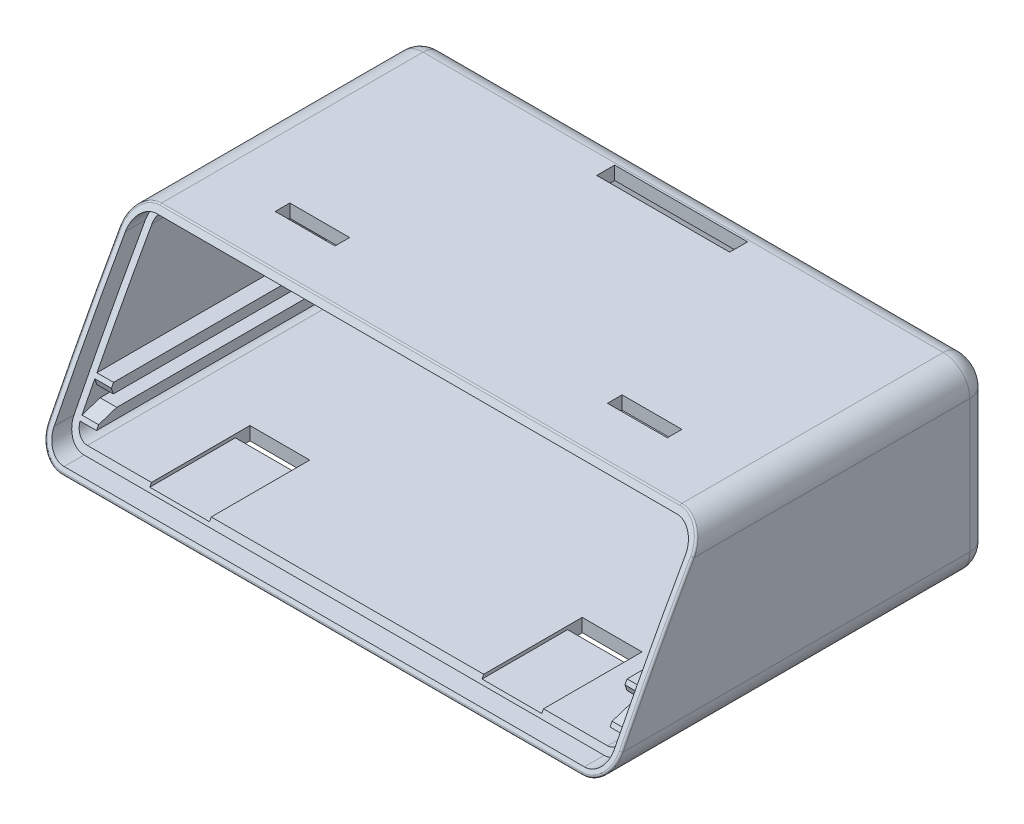
SolidWorks part; units mm, degrees
ref_plane "Front Plane" through (0, 0, 0) normal (0, 0, 1) x (1, 0, 0)
ref_plane "Top Plane" through (0, 0, 0) normal (0, 1, 0) x (1, 0, 0)
ref_plane "Right Plane" through (0, 0, 0) normal (1, 0, 0) x (0, 0, -1)
sketch "Sketch1" plane through (0, 0, 0) normal (0, 1, 0) x (1, 0, 0)
  line L1 (-43.14, -28.75) -> (43.14, -28.75)
  line L2 (-43.14, -28.75) -> (-43.14, 28.75)
  line L3 (-43.14, 28.75) -> (43.14, 28.75)
  line L4 (43.14, -28.75) -> (43.14, 28.75)
  line L5 (-43.14, -28.75) -> (43.14, 28.75) construction
  line L6 (-43.14, 28.75) -> (43.14, -28.75) construction
  point P0 (0, 0)
  dimension "D1" = 57.5
  dimension "D2" = 86.28
extrude "Boss-Extrude1" add sketch "Sketch1" along normal blind 28
fillet "Fillet1" radius 4 4 edges at (43.14, 28, 0) (43.14, 0, 0) (-43.14, 0, 0) (-43.14, 28, 0)
shell "Shell1" thickness 2
sketch "Sketch2" plane through (-43.14, 0, 0) normal (-1, 0, 0) x (0, 0, 1)
  line L0 (-28.75, 28) -> (28.75, 28) construction
  line L1 (13.75, 28) -> (28.75, 28)
  line L2 (28.75, 28) -> (28.75, 0)
  arc A0 (28.75, 0) -> (13.75, 28) centre (-397.2189, -210.1797) ccw
  dimension "D1" = 15
  dimension "D2" = 475
extrude "Cut-Extrude1" cut sketch "Sketch2" against normal through all
sketch "Sketch3" plane through (0, 0, -28.75) normal (0, 0, -1) x (-1, 0, 0)
  line L0 (-7.15, 18.7) -> (7.15, 18.7)
  line L1 (-6.95, 18.5) -> (6.95, 18.5) construction
  line L2 (-6.95, 18.5) -> (-6.95, 2.2) construction
  line L3 (-6.95, 2.2) -> (6.95, 2.2) construction
  line L4 (6.95, 18.5) -> (6.95, 2.2) construction
  line L5 (7.15, 18.7) -> (7.15, 2)
  line L6 (-7.15, 2) -> (7.15, 2)
  line L7 (-7.15, 18.7) -> (-7.15, 2)
  line L8 (27.25, 17.2) -> (38.3, 17.2)
  line L9 (27.45, 17) -> (38.1, 17) construction
  line L10 (27.45, 17) -> (27.45, 3.35) construction
  line L11 (27.45, 3.35) -> (38.1, 3.35) construction
  line L12 (38.1, 17) -> (38.1, 3.35) construction
  line L13 (38.3, 17.2) -> (38.3, 3.15)
  line L14 (27.25, 3.15) -> (38.3, 3.15)
  line L15 (27.25, 17.2) -> (27.25, 3.15)
  dimension "D1" = 0.2
  dimension "D2" = 0.2
extrude "Cut-Extrude2" cut sketch "Sketch3" against normal up to surface (2 mm away) up to face at (0, 14, -26.75)
fillet "Fillet2" radius 3 8 edges at (41.9684, 26.8284, -28.75) (43.14, 14, -28.75) (41.9684, 1.1716, -28.75) (0, 0, -28.75) (-41.9684, 1.1716, -28.75) (-43.14, 14, -28.75) (-41.9684, 26.8284, -28.75) (0, 28, -28.75)
sketch "Sketch4" plane through (0, 0, -26.75) normal (0, 0, 1) x (1, 0, 0)
  line L0 (-7.15, 2) -> (7.15, 2)
  line L1 (-7.15, 1) -> (7.15, 1)
  line L2 (7.15, 1) -> (39.14, 1)
  line L3 (42.14, 4) -> (42.14, 24)
  line L4 (39.14, 27) -> (-39.14, 27)
  line L5 (-42.14, 24) -> (-42.14, 4)
  line L6 (-39.14, 1) -> (-7.15, 1)
  line L8 (-7.15, 18.7) -> (7.15, 18.7)
  line L9 (7.15, 18.7) -> (7.15, 2)
  line L10 (7.15, 2) -> (39.14, 2)
  line L11 (41.14, 4) -> (41.14, 24)
  line L12 (39.14, 26) -> (-39.14, 26)
  line L13 (-41.14, 24) -> (-41.14, 4)
  line L14 (-39.14, 2) -> (-7.15, 2)
  line L15 (-7.15, 2) -> (-7.15, 18.7)
  line L18 (7.15, 2) -> (39.14, 2)
  line L19 (41.14, 4) -> (41.14, 24)
  line L20 (39.14, 26) -> (-39.14, 26)
  line L21 (-41.14, 24) -> (-41.14, 4)
  line L22 (-39.14, 2) -> (-7.15, 2)
  arc A0 (39.14, 1) -> (42.14, 4) centre (39.14, 4) ccw
  arc A1 (42.14, 24) -> (39.14, 27) centre (39.14, 24) ccw
  arc A2 (-39.14, 27) -> (-42.14, 24) centre (-39.14, 24) ccw
  arc A3 (-42.14, 4) -> (-39.14, 1) centre (-39.14, 4) ccw
  arc A4 (39.14, 2) -> (41.14, 4) centre (39.14, 4) ccw
  arc A5 (41.14, 24) -> (39.14, 26) centre (39.14, 24) ccw
  arc A6 (-39.14, 26) -> (-41.14, 24) centre (-39.14, 24) ccw
  arc A7 (-41.14, 4) -> (-39.14, 2) centre (-39.14, 4) ccw
  arc A8 (39.14, 2) -> (41.14, 4) centre (39.14, 4) ccw
  arc A9 (41.14, 24) -> (39.14, 26) centre (39.14, 24) ccw
  arc A10 (-39.14, 26) -> (-41.14, 24) centre (-39.14, 24) ccw
  arc A11 (-41.14, 4) -> (-39.14, 2) centre (-39.14, 4) ccw
  dimension "D1" = 0
  dimension "D2" = 1
extrude "Cut-Extrude3" cut sketch "Sketch4" against normal offset from surface (29.4971 mm away) 3 from offset 80
fillet "Fillet3" radius 0.3 8 edges at (41.7842, 27.0013, 14.3272) (43.14, 14.064, 21.517) (41.4452, 0.7311, 28.3885) (0, 0, 28.75) (-42.0581, 1.2642, 28.1239) (-43.14, 14.064, 21.517) (-41.3892, 27.3077, 14.1504) (0, 28, 13.75)
sketch "Sketch5" plane through (0, 0, -26.75) normal (0, 0, 1) x (1, 0, 0)
  line L0 (41.14, 24) -> (41.14, 4) construction
  line L1 (41.14, 5.25) -> (38.64, 5.25)
  line L2 (41.14, 5.25) -> (41.14, 3.75)
  line L3 (41.14, 3.75) -> (38.64, 3.75)
  line L4 (38.64, 5.25) -> (38.64, 3.75)
  line L5 (34.8894, 7.05) -> (40.64, 7.05) construction
  line L6 (41.14, 7.25) -> (38.64, 7.25)
  line L7 (41.14, 7.25) -> (41.14, 8.75)
  line L8 (41.14, 8.75) -> (38.64, 8.75)
  line L9 (38.64, 7.25) -> (38.64, 8.75)
  line L10 (-40.64, 7.05) -> (40.64, 7.05) construction
  line L11 (40.64, 5.45) -> (34.7752, 5.45) construction
  line L12 (-40.64, 5.45) -> (40.64, 5.45) construction
  line L13 (-41.14, 4) -> (-41.14, 24) construction
  line L14 (-41.14, 8.75) -> (-38.64, 8.75)
  line L15 (-41.14, 8.75) -> (-41.14, 7.25)
  line L16 (-41.14, 7.25) -> (-38.64, 7.25)
  line L17 (-38.64, 8.75) -> (-38.64, 7.25)
  line L19 (-41.14, 5.25) -> (-38.64, 5.25)
  line L20 (-41.14, 5.25) -> (-41.14, 3.75)
  line L21 (-41.14, 3.75) -> (-38.64, 3.75)
  line L22 (-38.64, 5.25) -> (-38.64, 3.75)
  dimension "D1" = 0.2
  dimension "D2" = 0.2
  dimension "D3" = 1.5
  dimension "D4" = 2.5
extrude "Boss-Extrude2" add sketch "Sketch5" along normal up to surface (49.8691 mm away)
sketch "Sketch6" plane through (0, 28, 0) normal (0, 1, 0) x (1, 0, 0)
  line L0 (0, 0) -> (0, 25.75) construction
  line L1 (-28.5, -4.13) -> (-28.5, -5.93) construction
  line L2 (21.5, -4.13) -> (28.5, -4.13) construction
  line L3 (21.5, -4.13) -> (21.5, -5.93) construction
  line L4 (21.5, -5.93) -> (28.5, -5.93) construction
  line L5 (28.5, -4.13) -> (28.5, -5.93) construction
  line L6 (20.5, -3.93) -> (29.5, -3.93)
  line L7 (20.5, -3.93) -> (20.5, -6.13)
  line L8 (20.5, -6.13) -> (29.5, -6.13)
  line L9 (39.14, 25.75) -> (-39.14, 25.75) construction
  line L10 (29.5, -3.93) -> (29.5, -6.13)
  line L11 (-21.5, -5.93) -> (-28.5, -5.93) construction
  line L12 (-21.5, -4.13) -> (-21.5, -5.93) construction
  line L13 (-21.5, -4.13) -> (-28.5, -4.13) construction
  line L14 (-29.5, -3.93) -> (-29.5, -6.13)
  line L15 (-20.5, -6.13) -> (-29.5, -6.13)
  line L16 (-20.5, -3.93) -> (-20.5, -6.13)
  line L17 (-20.5, -3.93) -> (-29.5, -3.93)
  dimension "D1" = 0.2
  dimension "D2" = 0.2
  dimension "D3" = 1
  dimension "D4" = 1
extrude "Cut-Extrude4" cut sketch "Sketch6" against normal up to surface (2 mm away) up to face at (0, 26, -7.4237)
sketch "Sketch9" plane through (0, 0, 0) normal (0, -1, 0) x (1, 0, 0)
  line L0 (0, 0) -> (0, 11.9026) construction
  line L1 (-28.5, 11.93) -> (-21.5, 11.93) construction
  line L2 (-28.5, 11.93) -> (-28.5, 10.13) construction
  line L3 (-28.5, 10.13) -> (-21.5, 10.13) construction
  line L4 (-21.5, 11.93) -> (-21.5, 10.13) construction
  line L5 (-29.5, 12.13) -> (-20.5, 12.13)
  line L6 (-29.5, 12.13) -> (-29.5, 9.93)
  line L7 (-29.5, 9.93) -> (-20.5, 9.93)
  line L8 (-20.5, 12.13) -> (-20.5, 9.93)
  line L9 (39.14, 11.9026) -> (-39.14, 11.9026) construction
  line L10 (21.5, 11.93) -> (21.5, 10.13) construction
  line L11 (28.5, 10.13) -> (21.5, 10.13) construction
  line L12 (28.5, 11.93) -> (28.5, 10.13) construction
  line L13 (28.5, 11.93) -> (21.5, 11.93) construction
  line L14 (20.5, 12.13) -> (20.5, 9.93)
  line L15 (29.5, 9.93) -> (20.5, 9.93)
  line L16 (29.5, 12.13) -> (29.5, 9.93)
  line L17 (29.5, 12.13) -> (20.5, 12.13)
  dimension "D1" = 0.2
  dimension "D2" = 0.2
  dimension "D3" = 1
  dimension "D4" = 1
extrude "Cut-Extrude7" cut sketch "Sketch9" against normal up to surface (2 mm away) up to face at (3.9988, 2, -14.1017)
sketch "Sketch7" plane through (0, 28, 0) normal (0, 1, 0) x (1, 0, 0)
  line L0 (-39.14, 28.75) -> (39.14, 28.75) construction
  line L1 (-10, 25.15) -> (10, 25.15)
  line L2 (-10, 25.15) -> (-10, 22.75)
  line L3 (-10, 22.75) -> (10, 22.75)
  line L4 (10, 25.15) -> (10, 22.75)
  line L5 (0, 22.75) -> (0, 0) construction
  dimension "D1" = 3.6
  dimension "D2" = 2.4
  dimension "D3" = 20
extrude "Cut-Extrude5" cut sketch "Sketch7" against normal up to surface (2 mm away) up to face at (-25, 26, 5.03)
sketch "Sketch8" plane through (0, 0, 6.13) normal (0, 0, -1) x (-1, 0, 0)
  line L0 (-29.5, 26) -> (-20.5, 26) construction
  line L1 (-29.5, 26) -> (-20.5, 26)
  line L2 (29.5, 26.5) -> (20.5, 26.5)
  line L3 (-20.5, 26.5) -> (-29.5, 26.5)
  line L4 (20.5, 26) -> (29.5, 26)
  line L5 (29.5, 26) -> (29.5, 28)
  line L6 (29.5, 28) -> (20.5, 28)
  line L7 (20.5, 28) -> (20.5, 26)
  line L8 (20.5, 26) -> (29.5, 26)
  line L9 (29.5, 26) -> (29.5, 26.5)
  line L10 (-20.5, 26.5) -> (-20.5, 26)
  line L11 (20.5, 26.5) -> (20.5, 26)
  line L12 (-29.5, 26.5) -> (-29.5, 26)
  line L14 (-29.5, 26) -> (-20.5, 26)
  line L15 (-20.5, 26) -> (-20.5, 28)
  line L16 (-20.5, 28) -> (-29.5, 28)
  line L17 (-29.5, 28) -> (-29.5, 26)
  line L18 (-29.5, 26) -> (-20.5, 26)
  dimension "D3" = 0.5
  dimension "D4" = 0.5
  dimension "D1" = 0
  dimension "D2" = 0
extrude "Cut-Extrude6" cut sketch "Sketch8" against normal through all
sketch "Sketch10" plane through (0, 0, 12.13) normal (0, 0, -1) x (-1, 0, 0)
  line L0 (29.5, 1.5) -> (20.5, 1.5)
  line L1 (-20.5, 1.5) -> (-29.5, 1.5)
  line L4 (-20.5, 2) -> (-29.5, 2)
  line L5 (-29.5, 2) -> (-29.5, 0)
  line L6 (-29.5, 0) -> (-20.5, 0)
  line L7 (-20.5, 0) -> (-20.5, 2)
  line L8 (-20.5, 2) -> (-29.5, 2)
  line L9 (-29.5, 2) -> (-29.5, 1.5)
  line L11 (-20.5, 1.5) -> (-20.5, 2)
  line L12 (29.5, 2) -> (20.5, 2)
  line L13 (20.5, 2) -> (20.5, 0)
  line L14 (20.5, 0) -> (29.5, 0)
  line L15 (29.5, 0) -> (29.5, 2)
  line L16 (29.5, 2) -> (20.5, 2)
  line L17 (20.5, 2) -> (20.5, 1.5)
  line L19 (29.5, 1.5) -> (29.5, 2)
  dimension "D3" = 0.5
  dimension "D1" = 0
  dimension "D2" = 0
extrude "Cut-Extrude8" cut sketch "Sketch10" against normal through all
sketch "Sketch11" plane through (0, 0, -26.75) normal (0, 0, 1) x (1, 0, 0)
  line L0 (-38.3, 3.15) -> (-38.3, 17.2) construction
  line L1 (-41.14, 5.25) -> (-38.3, 5.25)
  line L2 (-41.14, 5.25) -> (-41.14, 7.25)
  line L3 (-41.14, 7.25) -> (-38.3, 7.25)
  line L4 (-38.3, 5.25) -> (-38.3, 7.25)
  line L5 (-41.14, 7.25) -> (-38.64, 7.25) construction
  line L7 (41.14, 5.25) -> (7.15, 5.25)
  line L8 (41.14, 5.25) -> (41.14, 7.25)
  line L9 (41.14, 7.25) -> (7.15, 7.25)
  line L10 (7.15, 5.25) -> (7.15, 7.25)
  line L11 (-27.25, 17.2) -> (-27.25, 3.15) construction
  line L12 (-27.25, 5.25) -> (-7.15, 5.25)
  line L13 (-27.25, 5.25) -> (-27.25, 7.25)
  line L14 (-27.25, 7.25) -> (-7.15, 7.25)
  line L16 (-7.15, 5.25) -> (-7.15, 7.25)
  line L17 (-7.15, 2) -> (-7.15, 18.7) construction
  line L18 (7.15, 18.7) -> (7.15, 2) construction
  line L19 (38.64, 7.25) -> (41.14, 7.25) construction
extrude "Boss-Extrude3" add sketch "Sketch11" along normal blind 0.5
chamfer "Chamfer1" distance 1 angle 45 4 edges at (39.89, 5.25, 23.1191) (39.89, 7.25, 22.0954) (-39.89, 7.25, 22.0954) (-39.89, 5.25, 23.1191)
sketch "Sketch12" plane through (0, 0, -25.15) normal (0, 0, 1) x (1, 0, 0)
  line L4 (10, 26) -> (10, 28)
  line L5 (10, 28) -> (-10, 28)
  line L6 (-10, 28) -> (-10, 26)
  line L7 (-10, 26) -> (10, 26)
  line L8 (10, 26) -> (10, 28)
  line L9 (10, 28) -> (-10, 28)
  line L10 (-10, 28) -> (-10, 26)
  line L11 (-10, 26) -> (10, 26)
  dimension "D1" = 0
extrude "Cut-Extrude9" cut sketch "Sketch12" against normal blind 0.3
